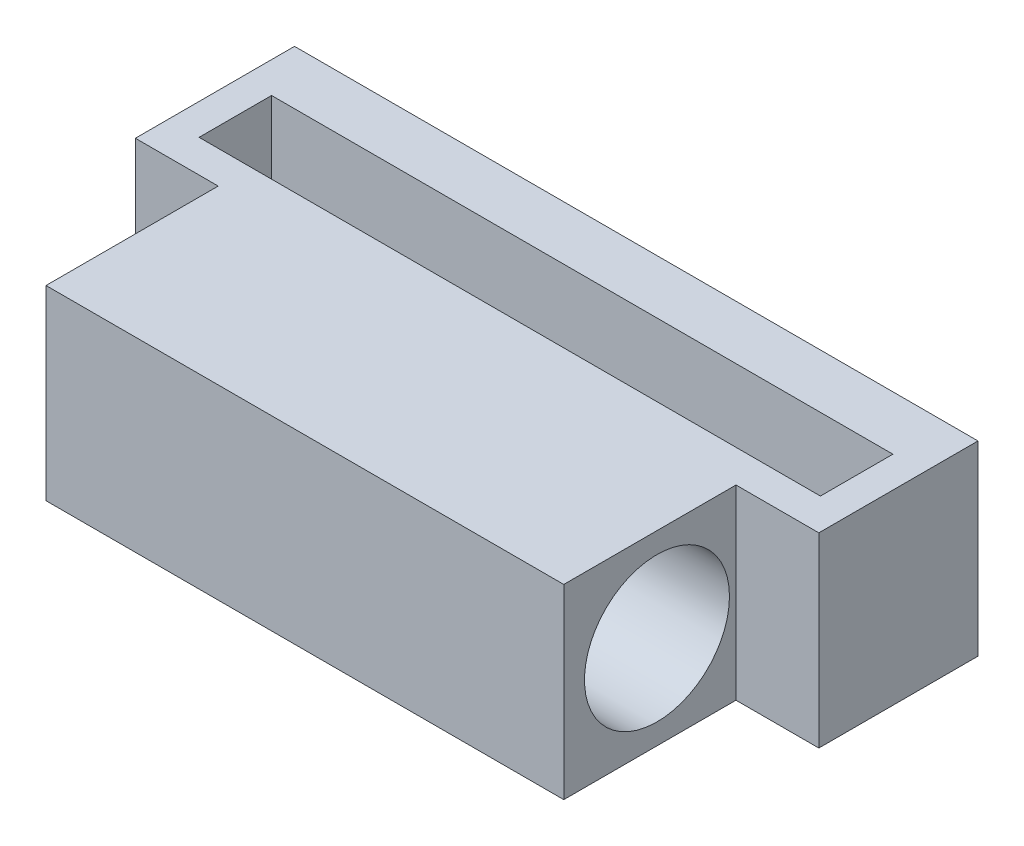
SolidWorks part; units mm, degrees
ref_plane "Plan de face" through (0, 0, 0) normal (0, 0, 1) x (1, 0, 0)
ref_plane "Plan de dessus" through (0, 0, 0) normal (0, 1, 0) x (1, 0, 0)
ref_plane "Plan de droite" through (0, 0, 0) normal (1, 0, 0) x (0, 0, -1)
sketch "Esquisse1" plane through (0, 0, 0) normal (0, 1, 0) x (1, 0, 0)
  line L1 (0, 0) -> (25, 0)
  line L2 (0, 0) -> (0, 16)
  line L3 (0, 16) -> (25, 16)
  line L4 (25, 0) -> (25, 16)
  dimension "D1" = 25
  dimension "D2" = 16
extrude "Boss.-Extru.1" add sketch "Esquisse1" along normal blind 9
sketch "Esquisse2" plane through (25, 0, 0) normal (1, 0, 0) x (0, 0, -1)
  line L0 (0, 9) -> (16, 9) construction
  line L1 (0, 9) -> (0, 0) construction
  circle A0 centre (4.5, 4.5) radius 3.5
  dimension "D3" = 7
  dimension "D1" = 4.5
  dimension "D2" = 4.5
extrude "Enlèv. mat.-Extru.1" cut sketch "Esquisse2" against normal through all
sketch "Esquisse3" plane through (0, 9, 0) normal (0, 1, 0) x (1, 0, 0)
  line L0 (25, 16) -> (0, 16) construction
  line L1 (-2.5, 13.3908) -> (27.5, 13.3908)
  line L2 (-2.5, 13.3908) -> (-2.5, 9.8908)
  line L3 (-2.5, 9.8908) -> (27.5, 9.8908)
  line L4 (27.5, 13.3908) -> (27.5, 9.8908)
  point P4 (12.5, 13.3908)
  point P7 (12.5, 16)
  dimension "D1" = 3.5
  dimension "D2" = 30
  dimension "D3" = 0
sketch "Esquisse5" plane through (25, 0, 0) normal (1, 0, 0) x (0, 0, -1)
  line L0 (0, 9) -> (16, 9) construction
  line L1 (8.315, 9) -> (16, 9)
  line L2 (8.315, 9) -> (8.315, 0)
  line L3 (8.315, 0) -> (16, 0)
  line L4 (16, 9) -> (16, 0)
extrude "Boss.-Extru.2" add sketch "Esquisse5" along normal blind 4 and the other way blind 29
extrude "Enlèv. mat.-Extru.3" cut sketch "Esquisse3" against normal through all
